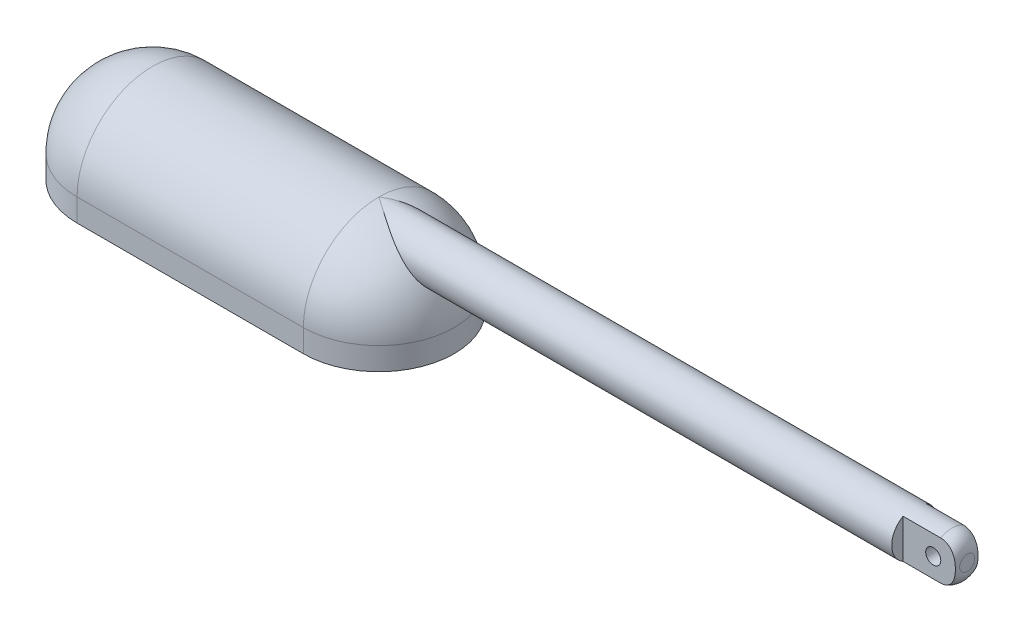
SolidWorks part; units mm, degrees
material "6061 Alloy"
ref_plane "Front Plane" through (0, 0, 0) normal (0, 0, 1) x (1, 0, 0)
ref_plane "Top Plane" through (0, 0, 0) normal (0, 1, 0) x (1, 0, 0)
ref_plane "Right Plane" through (0, 0, 0) normal (1, 0, 0) x (0, 0, -1)
sketch "Sketch1" plane through (0, 0, 0) normal (0, 0, 1) x (1, 0, 0)
  line L7 (485, 50) -> (485, 35)
  line L8 (485, 35) -> (130.7071, 35)
  line L9 (130.7071, 35) -> (130.7071, 50)
  line L10 (95, 50) -> (485, 50)
  line L12 (95, 50) -> (-55, 50)
  line L13 (70, 25) -> (-30, 25)
  line L15 (-55, 50) -> (95, 50)
  line L16 (-105, 0) -> (-55, 0)
  line L17 (-55, 0) -> (95, 0) construction
  line L19 (95, 0) -> (145, 0)
  arc A2 (70, 25) -> (95, 0) centre (70, 0) cw
  arc A3 (95, 50) -> (145, 0) centre (95, 0) cw
  arc A4 (-55, 50) -> (-105, 0) centre (-55, 0) ccw
  arc A5 (-30, 25) -> (-55, 0) centre (-30, 0) ccw
  dimension "D2" = 25
  dimension "D9" = 50
  dimension "D7" = 50
  dimension "D4" = 25
  dimension "D5" = 150
  dimension "D3" = 50
  dimension "D6" = 15
  dimension "D8" = 50
  dimension "D10" = 390
revolve "Revolve2" add sketch "Sketch1" angle 180 mid plane about L17 region at (20, 28.8433, 0)
revolve "Revolve3" add sketch "Sketch1<3>" angle 270 mid plane about L8 region at (307.8536, 42.5, 0) region at (122.0703, 45.6452, 0)
sketch "Sketch1<3>" plane through (0, 0, 0) normal (0, 0, 1) x (1, 0, 0) same geometry as "Sketch1"
revolve "Revolve4" add sketch "Sketch1<19>" angle 360 about L8 region at (307.8536, 42.5, 0)
sketch "Sketch1<19>" plane through (0, 0, 0) normal (0, 0, 1) x (1, 0, 0) same geometry as "Sketch1"
sketch "Sketch2" plane through (0, 0, 0) normal (0, -1, 0) x (1, 0, 0)
  line L2 (-55, -50) -> (95, -50)
  line L3 (95, 50) -> (-55, 50)
  line L4 (-55, -50) -> (95, -50)
  line L5 (95, 50) -> (-55, 50)
  arc A2 (95, -50) -> (95, 50) centre (95, 0) ccw
  arc A3 (-55, 50) -> (-55, -50) centre (-55, 0) ccw
  arc A4 (95, -50) -> (95, 50) centre (95, 0) ccw
  arc A5 (-55, 50) -> (-55, -50) centre (-55, 0) ccw
  line M5 (-55, -50) -> (95, -50)
  arc M6 (95, -50) -> (95, 50) centre (95, 0) ccw
  line M7 (95, 50) -> (-55, 50)
  arc M8 (-55, 50) -> (-55, -50) centre (-55, 0) ccw
  arc M9 (-30, -25) -> (-30, 25) centre (-30, 0) cw
  line M10 (-30, 25) -> (70, 25)
  arc M11 (70, 25) -> (70, -25) centre (70, 0) cw
  line M12 (70, -25) -> (-30, -25)
  dimension "D1" = 0
extrude "Boss-Extrude1" add sketch "Sketch2" along normal blind 15 contours M8 M5 M6 M7 M12 M9 M10 M11 region at (-102.3074, 0, 0)
sketch "Sketch5" plane through (0, 0, 0) normal (0, 0, 1) x (1, 0, 0)
  line L0 (485, 35) -> (470, 35) construction
  line L1 (485, 20) -> (485, 50) construction
  circle A0 centre (470, 35) radius 5
  dimension "D2" = 10
  dimension "D1" = 15
extrude "Cut-Extrude1" cut sketch "Sketch5" against normal up to next and the other way up to next
sketch "Sketch6" plane through (0, 0, 0) normal (0, 1, 0) x (1, 0, 0)
  line L1 (485, -15) -> (485, 15) construction
  line L2 (485, 7.5) -> (450, 7.5)
  line L4 (450, -7.5) -> (485, -7.5)
  line L5 (450, 7.5) -> (450, 15)
  line L6 (465, 15) -> (127.4037, 15) construction
  line L7 (450, 15) -> (485, 15)
  line L8 (485, 15) -> (485, 7.5)
  line L9 (485, -7.5) -> (485, -15)
  line L10 (485, -15) -> (450, -15)
  line L11 (450, -15) -> (450, -7.5)
  point P5 (495, 0)
  dimension "D1" = 35
  dimension "D2" = 35
extrude "Cut-Extrude6" cut sketch "Sketch6" against normal through all both and the other way through all
fillet "Fillet1" radius 10 1 edges at (485, 50, 0)
